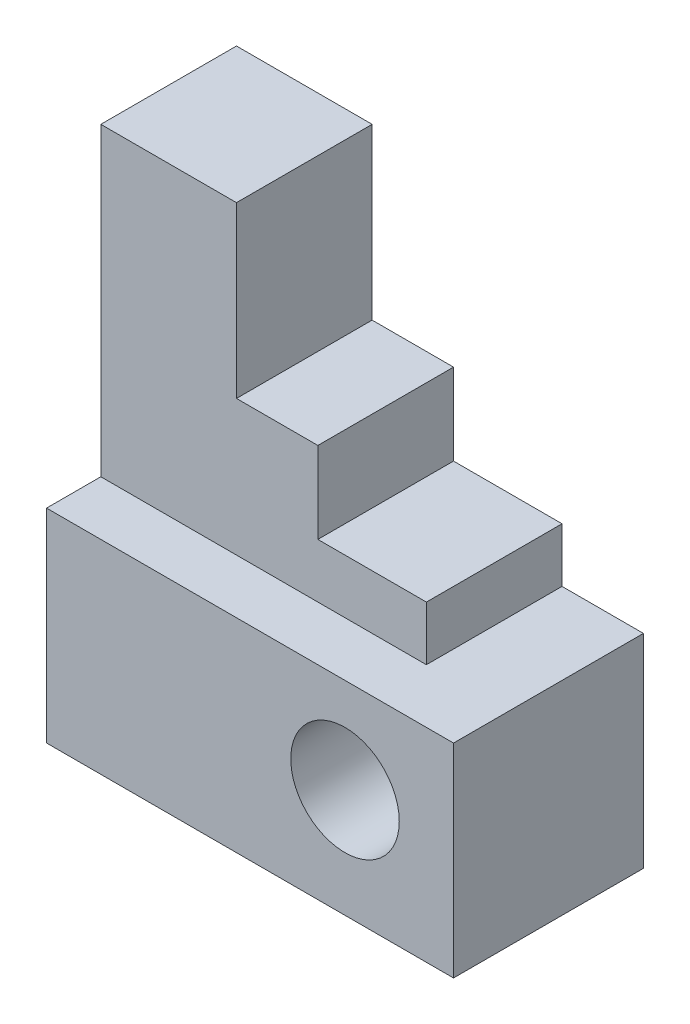
SolidWorks part; units mm, degrees
material "Aluminum Bronze"
ref_plane "Front Plane" through (0, 0, 0) normal (0, 0, 1) x (1, 0, 0)
ref_plane "Top Plane" through (0, 0, 0) normal (0, 1, 0) x (1, 0, 0)
ref_plane "Right Plane" through (0, 0, 0) normal (1, 0, 0) x (0, 0, -1)
sketch "Sketch1" plane through (0, 0, 0) normal (0, 0, 1) x (1, 0, 0)
  line L1 (0, 0) -> (60, 0)
  line L2 (0, 0) -> (0, 30)
  line L3 (0, 30) -> (60, 30)
  line L4 (60, 0) -> (60, 30)
  circle A0 centre (44, 16) radius 8
  dimension "D3" = 16
  dimension "D1" = 60
  dimension "D2" = 30
  dimension "D4" = 16
  dimension "D5" = 16
extrude "Boss-Extrude1" add sketch "Sketch1" along normal blind 28
sketch "Sketch2" plane through (0, 0, 0) normal (0, 0, 1) x (1, 0, 0)
  line L0 (0, 30) -> (0, 75)
  line L1 (0, 75) -> (20, 75)
  line L2 (20, 75) -> (20, 50)
  line L3 (20, 50) -> (32, 50)
  line L4 (32, 50) -> (32, 38)
  line L5 (32, 38) -> (48, 38)
  line L6 (48, 38) -> (48, 30)
  line L7 (60, 30) -> (0, 30) construction
  line L8 (48, 30) -> (0, 30)
  line L9 (0, 0) -> (60, 0) construction
  line L10 (60, 0) -> (60, 30) construction
  dimension "D1" = 75
  dimension "D2" = 12
  dimension "D3" = 12
  dimension "D4" = 12
  dimension "D5" = 20
  dimension "D6" = 20
extrude "Boss-Extrude2" add sketch "Sketch2" along normal blind 20
sketch "Sketch3" plane through (0, 0, 28) normal (0, 0, 1) x (1, 0, 0)
  line L0 (0, 0) -> (60, 0) construction
  line L1 (0, 0) -> (0, 30) construction
  circle A0 centre (16, 16) radius 6
  dimension "D3" = 12
  dimension "D1" = 16
  dimension "D2" = 16
